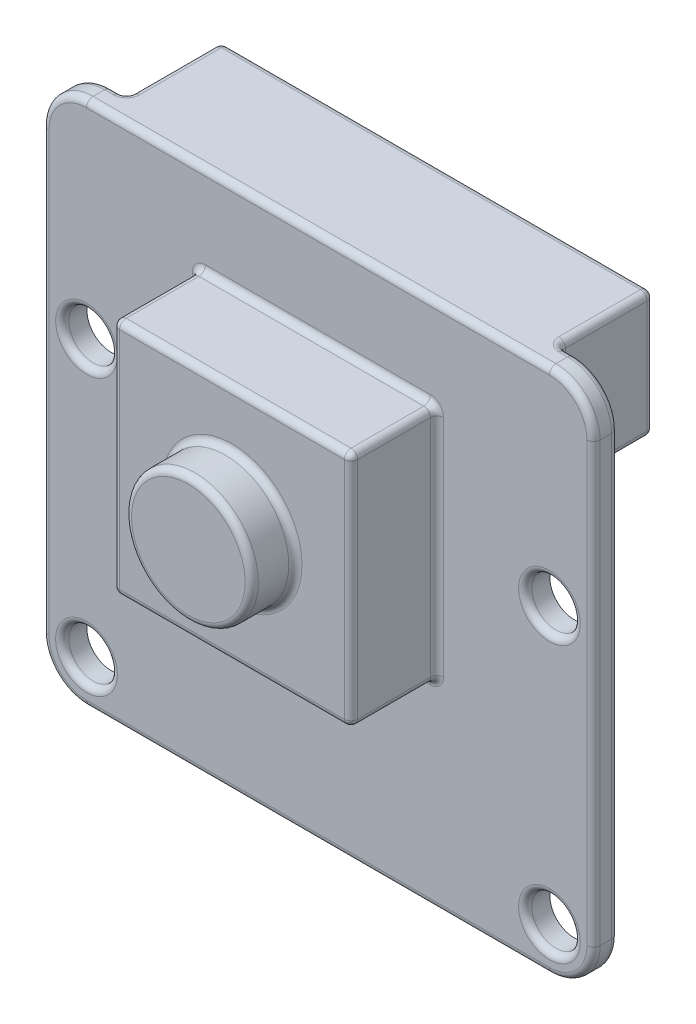
SolidWorks part; units mm, degrees
ref_plane "Front Plane" through (0, 0, 0) normal (0, 0, 1) x (1, 0, 0)
ref_plane "Top Plane" through (0, 0, 0) normal (0, 1, 0) x (1, 0, 0)
ref_plane "Right Plane" through (0, 0, 0) normal (1, 0, 0) x (0, 0, -1)
sketch "Sketch1" plane through (0, 0, 0) normal (0, 0, 1) x (1, 0, 0)
  line L1 (-12.5, 11.935) -> (12.5, 11.935)
  line L2 (-12.5, 11.935) -> (-12.5, -11.935)
  line L3 (-12.5, -11.935) -> (12.5, -11.935)
  line L4 (12.5, 11.935) -> (12.5, -11.935)
  line L5 (-12.5, 11.935) -> (12.5, -11.935) construction
  line L6 (-12.5, -11.935) -> (12.5, 11.935) construction
  point P0 (0, 0)
  dimension "D1" = 23.87
  dimension "D2" = 25
extrude "Boss-Extrude1" add sketch "Sketch1" along normal blind 1.12
sketch "Sketch2" plane through (0, 0, 1.12) normal (0, 0, 1) x (1, 0, 0)
  line L1 (-5.4, 7.865) -> (5.4, 7.865)
  line L2 (-5.4, 7.865) -> (-5.4, -2.935)
  line L3 (-5.4, -2.935) -> (5.4, -2.935)
  line L4 (5.4, 7.865) -> (5.4, -2.935)
  line L5 (-5.4, 7.865) -> (5.4, -2.935) construction
  line L6 (-5.4, -2.935) -> (5.4, 7.865) construction
  line L7 (-12.5, -11.935) -> (12.5, -11.935) construction
  point P0 (0, 2.465)
  dimension "D1" = 10.8
  dimension "D2" = 10.8
  dimension "D3" = 14.4
extrude "Boss-Extrude2" add sketch "Sketch2" along normal blind 3.9
sketch "Sketch3" plane through (0, 0, 5.02) normal (0, 0, 1) x (1, 0, 0)
  circle A0 centre (0, 2.465) radius 2.875
  dimension "D1" = 5.75
extrude "Boss-Extrude3" add sketch "Sketch3" along normal offset from surface (1.98 mm away) 7 up to face at (0, 0, 0)
sketch "Sketch4" plane through (0, 0, 1.12) normal (0, 0, 1) x (1, 0, 0)
  line L0 (-12.5, -11.935) -> (12.5, -11.935) construction
  line L1 (-12.5, 11.935) -> (-12.5, -11.935) construction
  line L2 (0, -11.935) -> (0, -8.3687) construction
  circle A0 centre (-10.5, 2.565) radius 1.1
  circle A1 centre (-10.5, -9.935) radius 1.1
  circle A2 centre (10.5, -9.935) radius 1.1
  circle A3 centre (10.5, 2.565) radius 1.1
  dimension "D1" = 2.2
  dimension "D3" = 2.2
  dimension "D4" = 2
  dimension "D2" = 14.5
  dimension "D5" = 2
  dimension "D6" = 2
extrude "Cut-Extrude1" cut sketch "Sketch4" against normal blind 7
fillet "Fillet1" radius 2 4 edges at (12.5, -11.935, 0.56) (-12.5, -11.935, 0.56) (12.5, 11.935, 0.56) (-12.5, 11.935, 0.56)
sketch "Sketch5" plane through (0, 0, 0) normal (0, 0, -1) x (-1, 0, 0)
  line L0 (-10.5, 11.935) -> (10.5, 11.935) construction
  line L1 (-9.805, 11.935) -> (9.805, 11.935)
  line L2 (-9.805, 11.935) -> (-9.805, 6.225)
  line L3 (-9.805, 6.225) -> (9.805, 6.225)
  line L4 (9.805, 11.935) -> (9.805, 6.225)
  line L5 (-9.805, 11.935) -> (9.805, 6.225) construction
  line L6 (-9.805, 6.225) -> (9.805, 11.935) construction
  line L7 (0, 11.935) -> (0, 14.0683) construction
  point P0 (0, 9.08)
  point P9 (0, 11.935)
  dimension "D1" = 19.61
  dimension "D2" = 5.71
extrude "Boss-Extrude4" add sketch "Sketch5" along normal offset from surface (4.3 mm away) 11.3 up to face at (2.875, 2.465, 7)
fillet "Fillet2" radius 0.3 34 edges at (0, -11.935, 0) (-11.9142, -11.3492, 0) (11.9142, -11.3492, 0) (-12.5, 0, 0) (12.5, 0, 0) (-11.9142, 11.3492, 0) (11.9142, 11.3492, 0) (-10.1525, 11.935, 0) (10.1525, 11.935, 0) (-5.4, 2.465, 1.12) (-5.4, -2.935, 3.07) (0, -2.935, 1.12) (5.4, -2.935, 3.07) (5.4, 2.465, 1.12) (5.4, 7.865, 3.07) (-5.4, 7.865, 3.07) (0, 7.865, 1.12) (0, -2.935, 5.02) (-5.4, 2.465, 5.02) (0, 7.865, 5.02) (5.4, 2.465, 5.02) (2.875, 2.465, 5.02) (2.875, 2.465, 7) (-9.805, 9.08, 0) (-9.805, 11.935, -2.15) (9.805, 9.08, 0) (9.805, 11.935, -2.15) (0, 6.225, 0) (9.805, 6.225, -2.15) (-9.805, 6.225, -2.15) (-9.805, 9.08, -4.3) (0, 6.225, -4.3) (9.805, 9.08, -4.3) (0, 11.935, -4.3)
fillet "Fillet3" radius 0.3 12 edges at (-11.9142, -11.3492, 1.12) (-12.5, 0, 1.12) (-11.9142, 11.3492, 1.12) (0, 11.935, 1.12) (11.9142, 11.3492, 1.12) (12.5, 0, 1.12) (11.9142, -11.3492, 1.12) (0, -11.935, 1.12) (-9.4, 2.565, 1.12) (-9.4, -9.935, 1.12) (9.4, -9.935, 1.12) (9.4, 2.565, 1.12)
sketch "Sketch6" plane through (0, 0, 7) normal (0, 0, 1) x (1, 0, 0)
  point P0 (0, 2.465)
sketch "Sketch7" plane through (0, 0, 7) normal (0, 0, 1) x (1, 0, 0)
  line L0 (0, 2.465) -> (0, 4.4177) construction
  line L3 (0, 2.465) -> (1.5211, 2.465) construction
ref_axis "Axis1" through (0, 2.465, 567.1851) along (0, 0, -1)
ref_axis "Axis2" through (-592.1945, 2.465, 7) along (1, 0, 0)
ref_axis "Axis3" through (0, -3210.6809, 7) along (0, 1, 0)
ref_plane "Plane1" through (0, 0, 0) normal (1, 0, 0) x (0, 0, -1)
ref_plane "Plane2" through (0, 2.465, 0) normal (0, 1, 0) x (1, 0, 0)
ref_plane "Plane3" through (0, 0, 7) normal (0, 0, 1) x (1, 0, 0)
